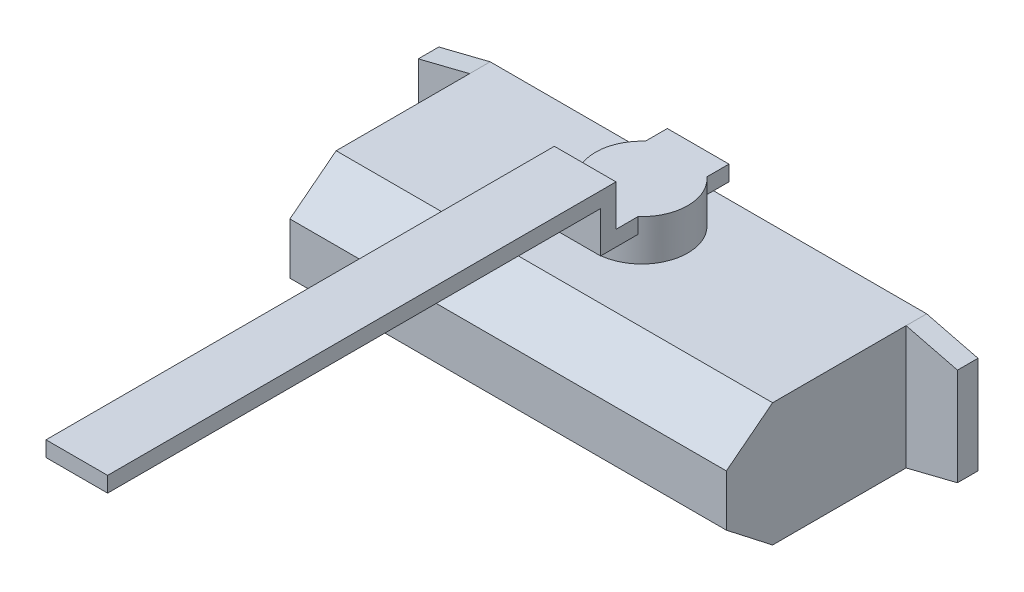
SolidWorks part; units mm, degrees
ref_plane "Front Plane" through (0, 0, 0) normal (0, 0, 1) x (1, 0, 0)
ref_plane "Top Plane" through (0, 0, 0) normal (0, 1, 0) x (1, 0, 0)
ref_plane "Right Plane" through (0, 0, 0) normal (1, 0, 0) x (0, 0, -1)
sketch "Sketch1" plane through (0, 0, 0) normal (0, 0, 1) x (1, 0, 0)
  line L1 (-67.4687, -19.05) -> (67.4688, -19.05)
  line L2 (-67.4687, -19.05) -> (-67.4687, 19.05)
  line L3 (-67.4687, 19.05) -> (67.4688, 19.05)
  line L4 (67.4688, -19.05) -> (67.4688, 19.05)
  line L5 (-67.4687, -19.05) -> (67.4688, 19.05) construction
  line L6 (-67.4687, 19.05) -> (67.4688, -19.05) construction
  point P0 (0, 0)
  dimension "D1" = 134.9375
  dimension "D2" = 38.1
extrude "Boss-Extrude1" add sketch "Sketch1" along normal blind 47.625
sketch "Sketch3" plane through (0, 0, 0) normal (0, 0, -1) x (-1, 0, 0)
  line L0 (-67.4688, 19.05) -> (-67.4688, -19.05)
  line L1 (-67.4688, -19.05) -> (-83.3438, -15.0812)
  line L2 (-83.3438, -15.0812) -> (-83.3438, 15.0813)
  line L3 (-83.3438, 15.0813) -> (-67.4688, 19.05)
  line L4 (0, 20.955) -> (0, -20.955) construction
  line L5 (67.4688, 19.05) -> (67.4688, -19.05)
  line L6 (67.4688, -19.05) -> (83.3438, -15.0812)
  line L7 (83.3438, -15.0812) -> (83.3438, 15.0813)
  line L8 (83.3438, 15.0813) -> (67.4688, 19.05)
  point P4 (-67.4688, 0)
  point P7 (-83.3438, 0)
  dimension "D1" = 30.1625
  dimension "D2" = 15.875
extrude "Boss-Extrude2" add sketch "Sketch3" against normal blind 6.35
sketch "Sketch4" plane through (67.4688, 0, 0) normal (1, 0, 0) x (0, 0, -1)
  line L0 (-47.625, 19.05) -> (-47.625, -19.05)
  line L1 (-47.625, -19.05) -> (-61.9125, -7.9375)
  line L2 (-61.9125, -7.9375) -> (-61.9125, 7.9375)
  line L3 (-61.9125, 7.9375) -> (-47.625, 19.05)
  point P4 (-61.9125, 0)
  point P7 (-47.625, 0)
  dimension "D1" = 15.875
  dimension "D2" = 14.2875
extrude "Boss-Extrude3" add sketch "Sketch4" against normal up to surface (134.9375 mm away) up to face at (-67.4688, 0, 26.9875)
shell "Shell1" thickness 1.5875 removed face at (0, 0, 0)
sketch "Sketch5" plane through (67.4688, 0, 0) normal (1, 0, 0) x (0, 0, -1)
  line L0 (-61.9125, 0) -> (-69.364, 0) construction
  line L2 (-61.9125, 7.9375) -> (-61.9125, -7.9375) construction
  circle A0 centre (-42.8625, 0) radius 16.6687
  dimension "D1" = 33.3375
  dimension "D2" = 19.05
sketch "Sketch6" plane through (65.8813, 0, 0) normal (-1, 0, 0) x (0, 0, 1)
  line L0 (-199938.0875, 0) -> (200069.364, 0) construction
  line L1 (-199938.0875, 0) -> (200069.364, 0)
  circle A0 centre (42.8625, 0) radius 16.6687 construction
  circle A1 centre (42.8625, 0) radius 16.6687
extrude "Boss-Extrude7" add sketch "Sketch6" along normal up to next contours A1
sketch "Sketch7" plane through (0, 19.05, 0) normal (0, 1, 0) x (1, 0, 0)
  line L0 (67.4688, 0) -> (-67.4688, 0) construction
  circle A0 centre (0, -20.6375) radius 14.2875
  point P2 (0, 0)
  dimension "D2" = 28.575
  dimension "D1" = 20.6375
extrude "Boss-Extrude8" add sketch "Sketch7" along normal blind 12.7
sketch "Sketch8" plane through (0, 31.75, 0) normal (0, 1, 0) x (1, 0, 0)
  line L1 (-9.525, -38.1) -> (9.525, -38.1)
  line L2 (-9.525, -38.1) -> (-9.525, -3.175)
  line L3 (-9.525, -3.175) -> (9.525, -3.175)
  line L4 (9.525, -38.1) -> (9.525, -3.175)
  line L5 (-9.525, -38.1) -> (9.525, -3.175) construction
  line L6 (-9.525, -3.175) -> (9.525, -38.1) construction
  point P0 (0, -20.6375)
  dimension "D1" = 17.4625
  dimension "D2" = 19.05
extrude "Boss-Extrude9" add sketch "Sketch8" against normal blind 4.7625
sketch "Sketch9" plane through (0, 0, 38.1) normal (0, 0, 1) x (1, 0, 0)
  line L0 (9.525, 31.75) -> (9.525, 26.9875) construction
  line L1 (-9.525, 26.9875) -> (9.525, 26.9875)
  line L2 (-9.525, 26.9875) -> (-9.525, 44.45)
  line L3 (-9.525, 44.45) -> (9.525, 44.45)
  line L4 (9.525, 26.9875) -> (9.525, 44.45)
  dimension "D1" = 17.4625
extrude "Boss-Extrude10" add sketch "Sketch9" along normal blind 4.7625
sketch "Sketch10" plane through (0, 0, 42.8625) normal (0, 0, 1) x (1, 0, 0)
  line L0 (9.525, 26.9875) -> (9.525, 44.45) construction
  line L1 (-9.525, 44.45) -> (9.525, 44.45)
  line L2 (-9.525, 44.45) -> (-9.525, 39.6875)
  line L3 (-9.525, 39.6875) -> (9.525, 39.6875)
  line L4 (9.525, 44.45) -> (9.525, 39.6875)
  dimension "D1" = 4.7625
extrude "Boss-Extrude11" add sketch "Sketch10" along normal blind 152.4
